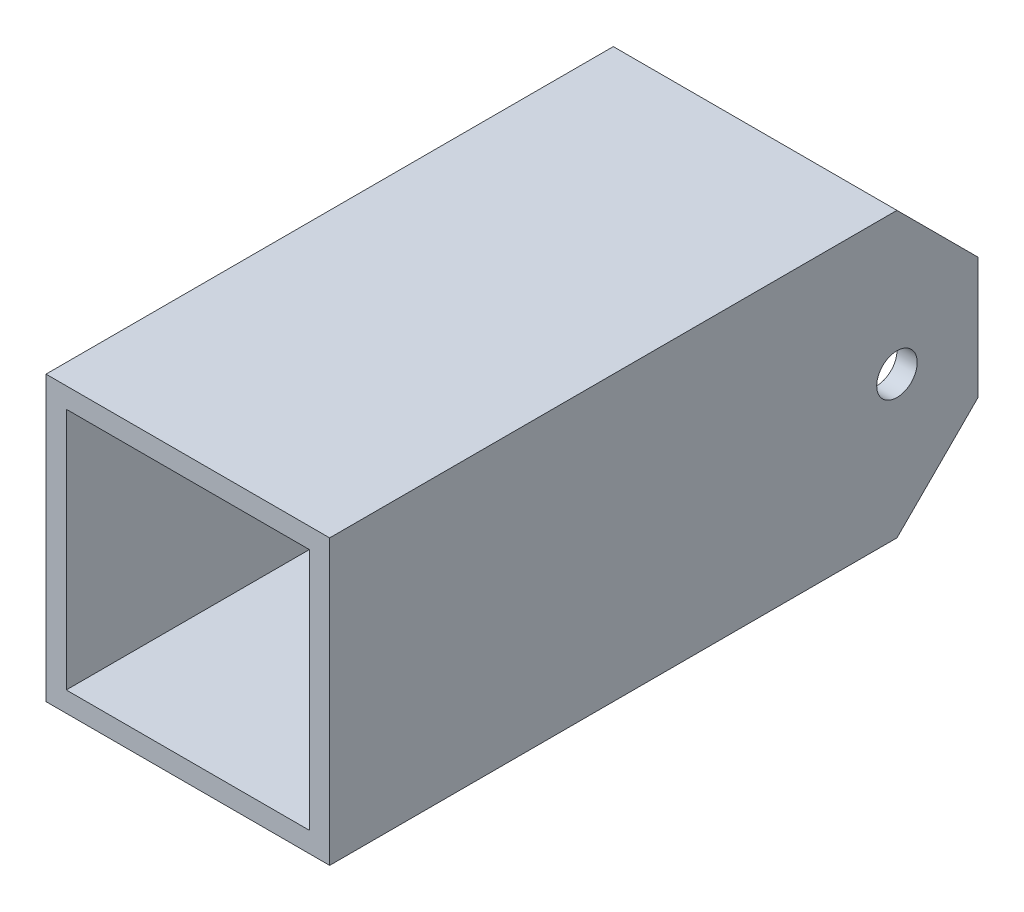
SolidWorks part; units mm, degrees
ref_plane "Front Plane" through (0, 0, 0) normal (0, 0, 1) x (1, 0, 0)
ref_plane "Top Plane" through (0, 0, 0) normal (0, 1, 0) x (1, 0, 0)
ref_plane "Right Plane" through (0, 0, 0) normal (1, 0, 0) x (0, 0, -1)
sketch "Sketch2" plane through (0, 0, 0) normal (0, 0, 1) x (1, 0, 0)
  line L1 (-22.225, 22.225) -> (22.225, 22.225)
  line L2 (-22.225, 22.225) -> (-22.225, -22.225)
  line L3 (-22.225, -22.225) -> (22.225, -22.225)
  line L4 (22.225, 22.225) -> (22.225, -22.225)
  line L5 (-22.225, 22.225) -> (22.225, -22.225) construction
  line L6 (-22.225, -22.225) -> (22.225, 22.225) construction
  line L7 (-19.05, 19.05) -> (19.05, 19.05)
  line L8 (-19.05, 19.05) -> (-19.05, -19.05)
  line L9 (-19.05, -19.05) -> (19.05, -19.05)
  line L10 (19.05, 19.05) -> (19.05, -19.05)
  line L11 (-19.05, 19.05) -> (19.05, -19.05) construction
  line L12 (-19.05, -19.05) -> (19.05, 19.05) construction
  point P0 (0, 0)
  point P6 (0, 0)
  dimension "D1" = 44.45
  dimension "D2" = 44.45
  dimension "D3" = 38.1
  dimension "D4" = 38.1
extrude "Boss-Extrude1" add sketch "Sketch2" along normal blind 101.6
sketch "Sketch5" plane through (-22.225, 0, 0) normal (-1, 0, 0) x (0, 0, 1)
  line L0 (101.6, 22.225) -> (0, 22.225) construction
  line L3 (0, 22.225) -> (0, -22.225) construction
  circle A0 centre (12.7, 0) radius 3.175
  dimension "D1" = 6.35
  dimension "D3" = 12.7
  dimension "D2" = 22.225
extrude "Cut-Extrude1" cut sketch "Sketch5" against normal blind 54.864
chamfer "Chamfer1" distance 12.7 angle 45 2 edges at (0, -22.225, 0) (0, 22.225, 0)
